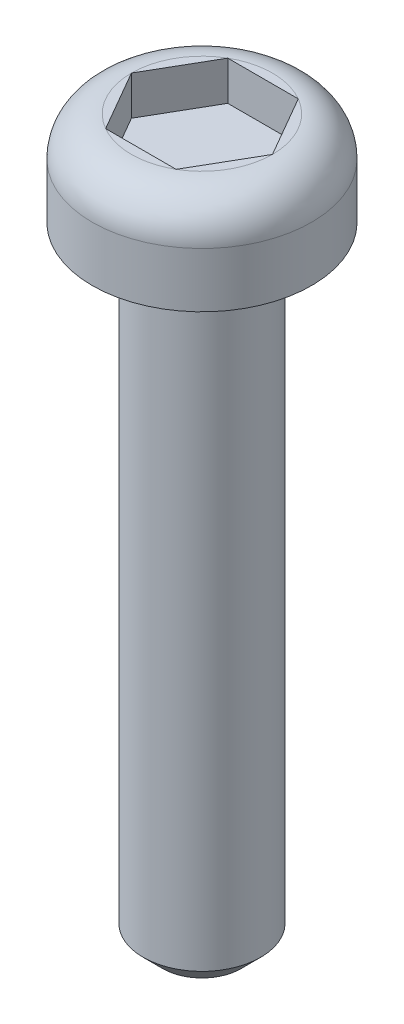
SolidWorks part; units mm, degrees
ref_plane "Front" through (0, 0, 0) normal (0, 0, 1) x (1, 0, 0)
ref_plane "Top" through (0, 0, 0) normal (0, 1, 0) x (1, 0, 0)
ref_plane "Right" through (0, 0, 0) normal (1, 0, 0) x (0, 0, -1)
sketch "Sketch1" plane through (0, 0, 0) normal (0, 1, 0) x (1, 0, 0)
  circle A0 centre (0, 0) radius 1.5
  dimension "D1" = 3
extrude "Boss-Extrude1" add sketch "Sketch1" along normal blind 16
cosmetic thread "Cosmetic Thread1" parameters "D2"=2
sketch "Sketch2" plane through (0, 16, 0) normal (0, 1, 0) x (1, 0, 0)
  circle A0 centre (0, 0) radius 2.8
  dimension "D1" = 5.6
extrude "Boss-Extrude2" add sketch "Sketch2" along normal blind 2.4
fillet "Fillet1" radius 1 1 edges at (0, 18.4, 2.8)
sketch "Sketch3" plane through (0, 18.4, 0) normal (0, 1, 0) x (1, 0, 0)
  line L1 (1.8, 0) -> (0.9, 1.5588)
  line L2 (0.9, 1.5588) -> (-0.9, 1.5588)
  line L3 (-0.9, 1.5588) -> (-1.8, 0)
  line L4 (-1.8, 0) -> (-0.9, -1.5588)
  line L5 (-0.9, -1.5588) -> (0.9, -1.5588)
  line L6 (0.9, -1.5588) -> (1.8, 0)
  circle A0 centre (0, 0) radius 1.5588 construction
  circle A1 centre (0, 0) radius 1.8 construction
  point P1 (1.8, 0)
  point P12 (0, 0)
extrude "Cut-Extrude1" cut sketch "Sketch3" against normal blind 1
chamfer "Chamfer1" distance 0.5 angle 45 1 edges at (0, 0, 1.5)
